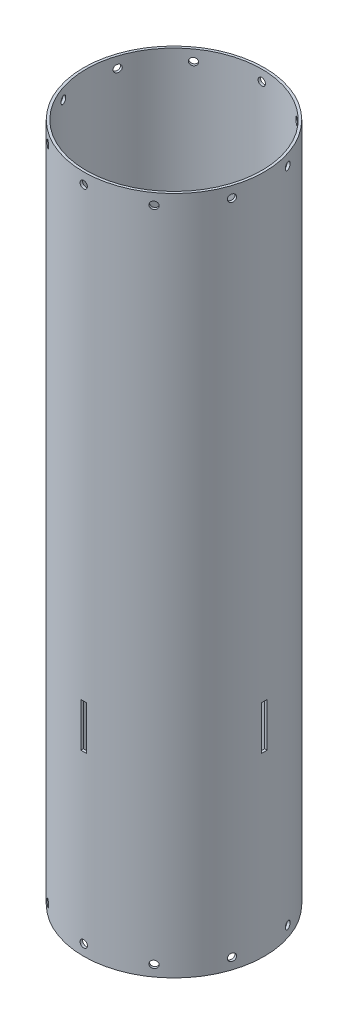
SolidWorks part; units mm, degrees
material "Acrylic (Medium-high impact)"
ref_plane "Front Plane" through (0, 0, 0) normal (0, 0, 1) x (1, 0, 0)
ref_plane "Top Plane" through (0, 0, 0) normal (0, 1, 0) x (1, 0, 0)
ref_plane "Right Plane" through (0, 0, 0) normal (1, 0, 0) x (0, 0, -1)
sketch "Sketch1" plane through (0, 0, 0) normal (0, 1, 0) x (1, 0, 0)
  circle A0 centre (0, 0) radius 76.2
  circle A1 centre (0, 0) radius 78.359
  dimension "D1" = 152.4
  dimension "D2" = 156.718
extrude "Boss-Extrude1" add sketch "Sketch1" along normal blind 589.28
sketch "Sketch2" plane through (0, 0, 0) normal (0, 0, 1) x (1, 0, 0)
  line L0 (0, 0) -> (0, 105.6712) construction
  line L1 (-76.2, 0) -> (76.2, 0) construction
  line L2 (-78.359, 0) -> (78.359, 0) construction
  line L3 (78.359, 294.64) -> (42.8908, 294.64) construction
  line L4 (78.359, 0) -> (78.359, 589.28) construction
  circle A0 centre (0, 9.525) radius 3.175
  circle A1 centre (0, 579.755) radius 3.175
  dimension "D1" = 6.35
  dimension "D2" = 9.525
extrude "Cut-Extrude1" cut sketch "Sketch2" against normal through all
ref_axis "Axis1" through (0, 0, 0) along (0, 1, 0)
pattern_circular "CirPattern1" count 10 over 360 about axis through (0, 0, 0) along (0, 1, 0) of "Cut-Extrude1" reverse direction yes
sketch "Sketch3" plane through (0, 0, 0) normal (0, 0, 1) x (1, 0, 0)
  line L0 (0, 0) -> (0, 105.6712) construction
  line L1 (-2.54, 153.67) -> (2.54, 153.67)
  line L2 (-2.54, 153.67) -> (-2.54, 191.77)
  line L3 (-2.54, 191.77) -> (2.54, 191.77)
  line L4 (2.54, 153.67) -> (2.54, 191.77)
  line L5 (-2.54, 153.67) -> (2.54, 191.77) construction
  line L6 (-2.54, 191.77) -> (2.54, 153.67) construction
  line L7 (-76.2, 0) -> (76.2, 0) construction
  line L8 (0, 589.28) -> (0, 408.1695) construction
  line L9 (76.2, 589.28) -> (-76.2, 589.28) construction
  point P0 (0, 172.72)
  dimension "D1" = 153.67
  dimension "D2" = 38.1
  dimension "D3" = 5.08
extrude "Cut-Extrude2" cut sketch "Sketch3" against normal through all
ref_axis "Axis2" through (0, 589.28, 0) along (0, -1, 0)
pattern_circular "CirPattern2" count 4 over 360 about axis through (0, 589.28, 0) along (0, -1, 0) of "Cut-Extrude2"
